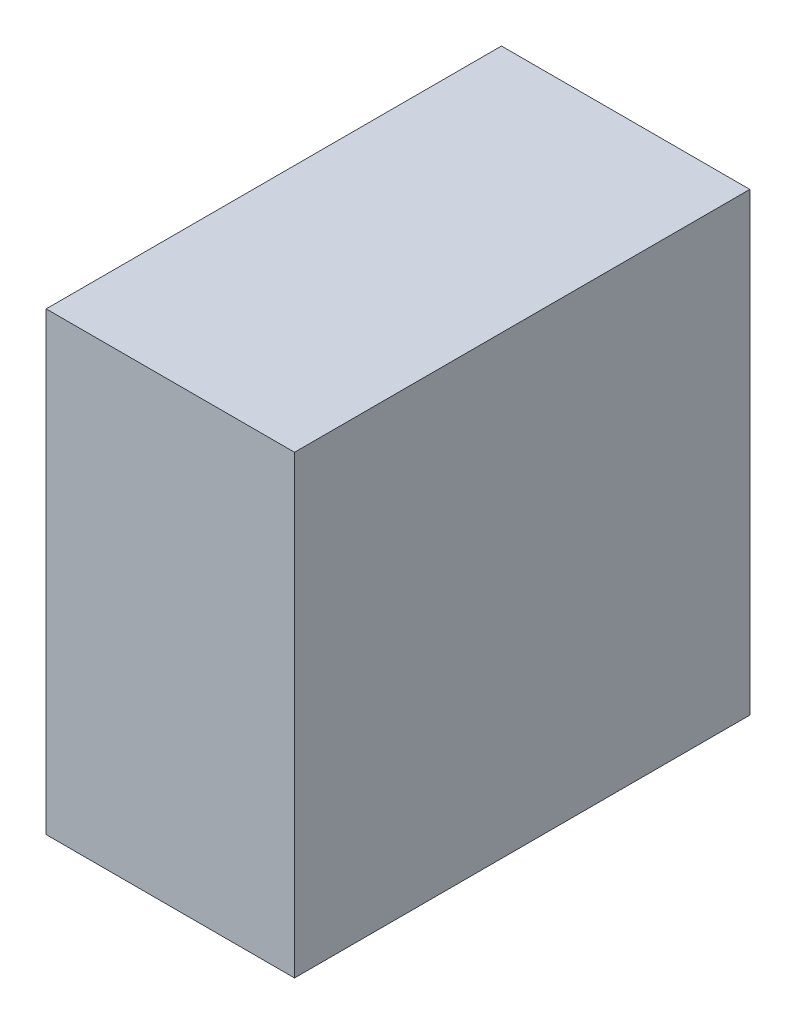
SolidWorks part; units mm, degrees
material "山毛榉"
ref_plane "前视基准面" through (0, 0, 0) normal (0, 0, 1) x (1, 0, 0)
ref_plane "上视基准面" through (0, 0, 0) normal (0, 1, 0) x (1, 0, 0)
ref_plane "右视基准面" through (0, 0, 0) normal (1, 0, 0) x (0, 0, -1)
sketch "草图1" plane through (0, 0, 0) normal (1, 0, 0) x (0, 0, -1)
  line L5 (56.0822, 53.2) -> (-53.9178, 53.2)
  line L6 (56.0822, 53.2) -> (56.0822, -56.8)
  line L7 (56.0822, -56.8) -> (-53.9178, -56.8)
  line L8 (-53.9178, 53.2) -> (-53.9178, -56.8)
  dimension "D1" = 110
  dimension "D2" = 110
extrude "凸台-拉伸2" add sketch "草图1" along normal blind 60
